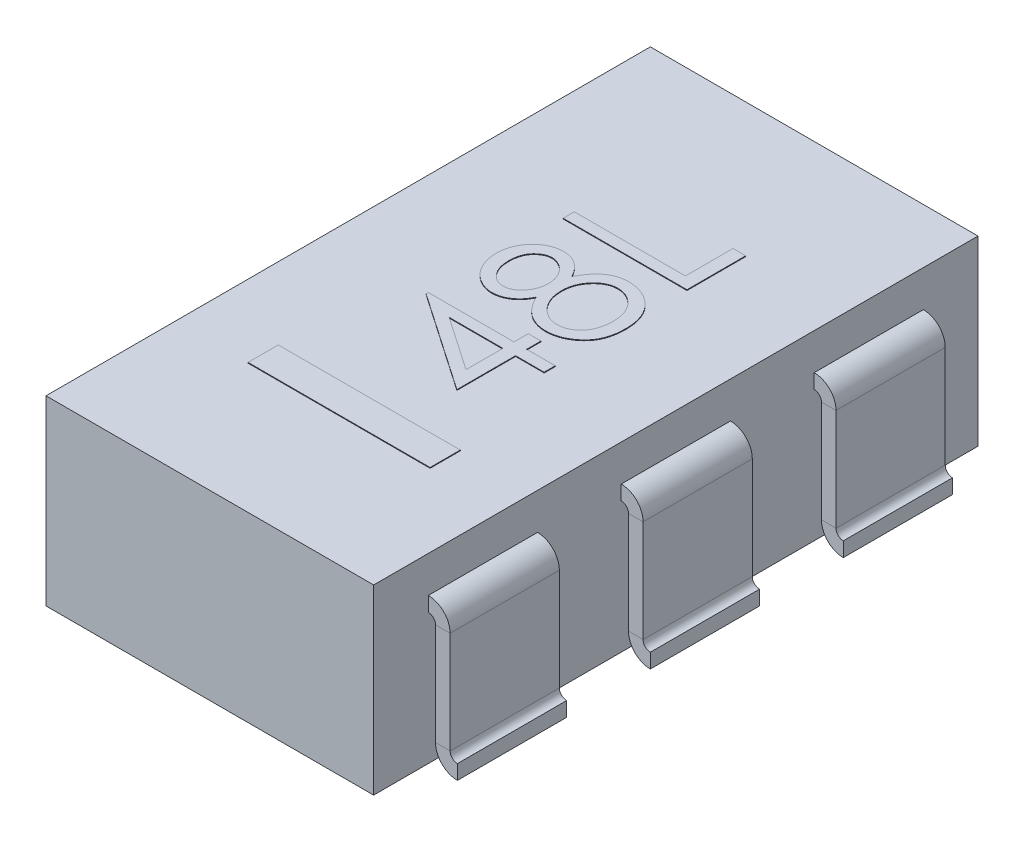
SolidWorks part; units mm, degrees
ref_plane "Front Plane" through (0, 0, 0) normal (0, 0, 1) x (1, 0, 0)
ref_plane "Top Plane" through (0, 0, 0) normal (0, 1, 0) x (1, 0, 0)
ref_plane "Right Plane" through (0, 0, 0) normal (1, 0, 0) x (0, 0, -1)
sketch "Sketch1" plane through (0, 0, 0) normal (0, 1, 0) x (1, 0, 0)
  line L1 (-0.5715, 1.0541) -> (0.5715, 1.0541)
  line L2 (-0.5715, 1.0541) -> (-0.5715, -1.0541)
  line L3 (-0.5715, -1.0541) -> (0.5715, -1.0541)
  line L4 (0.5715, 1.0541) -> (0.5715, -1.0541)
  point P4 (0.5715, 0)
  point P6 (0, 1.0541)
  dimension "D1" = 1.143
  dimension "D2" = 2.1082
extrude "Boss-Extrude1" add sketch "Sketch1" along normal blind 0.635
sketch "Sketch2" plane through (0.5715, 0, 0) normal (1, 0, 0) x (0, 0, -1)
  line L0 (-1.0541, 0.635) -> (1.0541, 0.635) construction
  line L1 (-0.8636, 0.508) -> (-0.4826, 0.508)
  line L2 (-0.8636, 0.508) -> (-0.8636, 0.4572)
  line L3 (-0.8636, 0.4572) -> (-0.4826, 0.4572)
  line L4 (-0.4826, 0.508) -> (-0.4826, 0.4572)
  line L5 (0.4826, 0.508) -> (0.8636, 0.508)
  line L6 (0.4826, 0.508) -> (0.4826, 0.4572)
  line L7 (0.4826, 0.4572) -> (0.8636, 0.4572)
  line L8 (0.8636, 0.508) -> (0.8636, 0.4572)
  line L9 (0.1905, 0.508) -> (-0.1905, 0.508) construction
  line L10 (0.1905, 0.508) -> (0.1905, 0.4572) construction
  line L11 (0.1905, 0.4572) -> (-0.1905, 0.4572) construction
  line L12 (-0.1905, 0.508) -> (-0.1905, 0.4572) construction
  line L13 (-0.1905, 0.508) -> (-0.4826, 0.508) construction
  line L14 (0.1905, 0.508) -> (0.4826, 0.508) construction
  line L15 (-1.0541, 0) -> (1.0541, 0) construction
  line L16 (1.0541, 0.635) -> (1.0541, 0) construction
  point P12 (0, 0.508)
  point P15 (0, 0)
  dimension "D1" = 0.127
  dimension "D2" = 0.381
  dimension "D3" = 0.0508
  dimension "D4" = 0.1905
sketch "Sketch3" plane through (0, 0, 0) normal (0, 0, 1) x (1, 0, 0)
  line L0 (0.5715, 0.4572) -> (0.5969, 0.4572) construction
  line L1 (0.5969, 0.4572) -> (0.5969, 0.4318) construction
  line L2 (0.5969, 0.4318) -> (0.5969, 0.0762)
  line L3 (0.5969, 0.0762) -> (0.5969, 0) construction
  line L4 (0.5969, 0) -> (0.6731, 0) construction
  line L5 (-0.5715, 0) -> (0.5715, 0) construction
  arc A0 (0.5715, 0.4572) -> (0.5969, 0.4318) centre (0.5715, 0.4318) cw
  arc A1 (0.5969, 0.0762) -> (0.6731, 0) centre (0.6731, 0.0762) ccw
  dimension "D1" = 0.0254
  dimension "D2" = 0.0762
sweep "Sweep1" add profiles "Sketch2" path "Sketch3"
mirror "Mirror1" about plane through (0, 0, 0) normal (1, 0, 0) of "Sweep1"
sketch "Sketch4" plane through (0.5715, 0, 0) normal (1, 0, 0) x (0, 0, -1)
  line L1 (-0.1905, 0.508) -> (0.1905, 0.508)
  line L2 (-0.1905, 0.508) -> (-0.1905, 0.4572)
  line L3 (-0.1905, 0.4572) -> (0.1905, 0.4572)
  line L4 (0.1905, 0.508) -> (0.1905, 0.4572)
sweep "Sweep2" add profiles "Sketch4" path "Sketch3<2>"
sketch "Sketch3<2>" plane through (0, 0, 0) normal (0, 0, 1) x (1, 0, 0) same geometry as "Sketch3"
sketch "Sketch5" plane through (0, 0.635, 0) normal (0, 1, 0) x (1, 0, 0)
  line L0 (0.2286, -0.6033) -> (0.2286, 0.6033) construction
  line L1 (-0.5715, -1.0541) -> (0.5715, -1.0541) construction
  line L2 (0.3175, -0.6033) -> (-0.3175, -0.6033)
  line L3 (0.3175, -0.6033) -> (0.3175, -0.4979)
  line L4 (0.3175, -0.4979) -> (-0.3175, -0.4979)
  line L5 (-0.3175, -0.6033) -> (-0.3175, -0.4979)
  text T0 "48L" font "Century Gothic" height 0.4318
  point P3 (0.2286, 0)
  point P10 (0, -0.4979)
  point P13 (0, -1.0541)
  dimension "D1" = 0.2286
  dimension "D2" = 0.635
extrude "Boss-Extrude2" add sketch "Sketch5" along normal blind 0.0025
